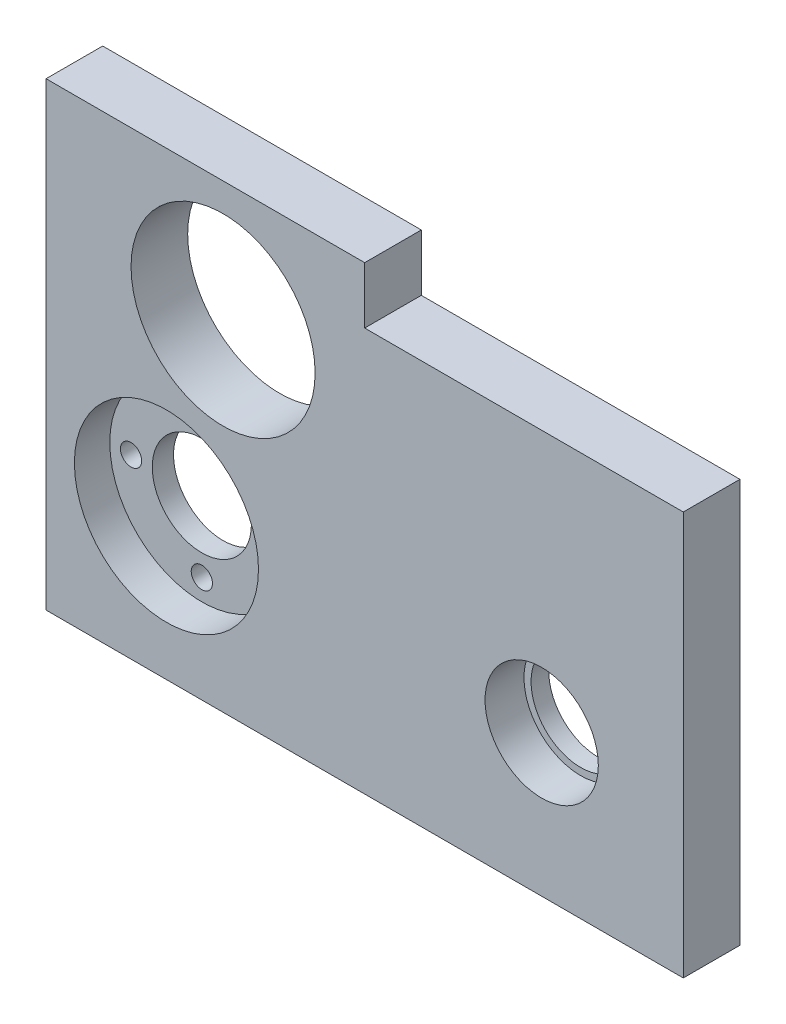
SolidWorks part; units mm, degrees
ref_plane "Front" through (0, 0, 0) normal (0, 0, 1) x (1, 0, 0)
ref_plane "Top" through (0, 0, 0) normal (0, 1, 0) x (1, 0, 0)
ref_plane "Right" through (0, 0, 0) normal (1, 0, 0) x (0, 0, -1)
sketch "Esquisse1" plane through (0, 0, 0) normal (0, 0, 1) x (1, 0, 0)
  line L1 (0, 0) -> (90, 0)
  line L2 (0, 0) -> (0, 65)
  line L3 (0, 65) -> (90, 65)
  line L4 (90, 0) -> (90, 65)
  circle A0 centre (70, 20) radius 7
  circle A1 centre (17, 20) radius 13
  circle A2 centre (25, 48) radius 13
  dimension "D3" = 14
  dimension "D4" = 20
  dimension "D6" = 53
  dimension "D8" = 26
  dimension "D9" = 26
  dimension "D1" = 90
  dimension "D2" = 65
  dimension "D5" = 70
  dimension "D7" = 20
  dimension "D10" = 53
  dimension "D11" = 48
extrude "Boss.-Extru.1" add sketch "Esquisse1" along normal blind 8
sketch "Esquisse2" plane through (0, 0, 0) normal (0, 0, -1) x (-1, 0, 0)
  circle A0 centre (-17, 20) radius 13
  circle A1 centre (-17, 20) radius 13 construction
extrude "Boss.-Extru.2" add sketch "Esquisse2" against normal blind 3
sketch "Esquisse3" plane through (0, 0, 3) normal (0, 0, 1) x (1, 0, 0)
  line L0 (27, 20) -> (17, 20) construction
  circle A0 centre (17, 20) radius 7
  circle A1 centre (27, 20) radius 1.5
  circle A2 centre (17, 10) radius 1.5
  circle A3 centre (7, 20) radius 1.5
  circle A4 centre (17, 30) radius 1.5
  point P13 (17, 20)
  dimension "D1" = 14
  dimension "D2" = 3
  dimension "D3" = 10
  dimension "D4" = 4
extrude "Enlèv. mat.-Extru.1" cut sketch "Esquisse3" against normal through all
sketch "Esquisse4" plane through (0, 0, 8) normal (0, 0, 1) x (1, 0, 0)
  circle A0 centre (70, 20) radius 8
  dimension "D1" = 16
extrude "Enlèv. mat.-Extru.2" cut sketch "Esquisse4" against normal blind 5.5
sketch "Esquisse5" plane through (0, 0, 8) normal (0, 0, 1) x (1, 0, 0)
  line L0 (90, 65) -> (0, 65) construction
  line L1 (45, 65) -> (90, 65)
  line L2 (45, 65) -> (45, 57)
  line L3 (45, 57) -> (90, 57)
  line L4 (90, 65) -> (90, 57)
  line L5 (90, 0) -> (90, 65) construction
  dimension "D1" = 8
  dimension "D2" = 45
extrude "Enlèv. mat.-Extru.3" cut sketch "Esquisse5" against normal through all
sketch "Esquisse6" plane through (0, 0, 0) normal (-1, 0, 0) x (0, 0, 1)
  line L0 (4, 0) -> (4, 65) construction
  line L1 (8, 0) -> (0, 0) construction
  line L2 (8, 65) -> (0, 65) construction
  circle A0 centre (4, 7) radius 1.65
  circle A1 centre (4, 35) radius 1.65
  dimension "D1" = 3.3
  dimension "D2" = 28
  dimension "D3" = 7
extrude "Enlèv. mat.-Extru.4" cut sketch "Esquisse6" against normal blind 10
